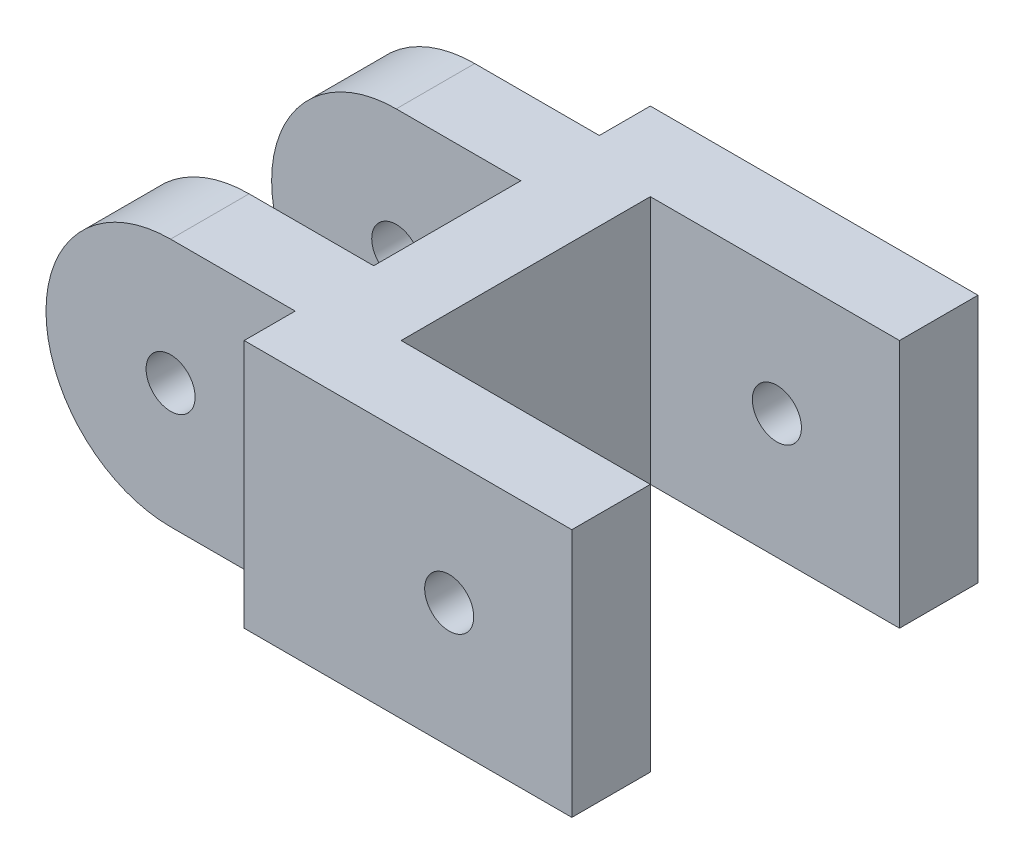
SolidWorks part; units mm, degrees
ref_plane "Front Plane" through (0, 0, 0) normal (0, 0, 1) x (1, 0, 0)
ref_plane "Top Plane" through (0, 0, 0) normal (0, 1, 0) x (1, 0, 0)
ref_plane "Right Plane" through (0, 0, 0) normal (1, 0, 0) x (0, 0, -1)
sketch "Sketch1" plane through (0, 0, 0) normal (0, 1, 0) x (1, 0, 0)
  line L0 (10.375, 15.95) -> (-15.025, 15.95)
  line L1 (-15.025, 15.95) -> (-15.025, -9.45)
  line L2 (-15.025, -9.45) -> (10.375, -9.45)
  line L3 (10.375, -9.45) -> (10.375, -17.45)
  line L4 (10.375, -17.45) -> (-23.025, -17.45)
  line L5 (-23.025, -17.45) -> (-23.025, -12.25)
  line L6 (-23.025, -12.25) -> (-48.425, -12.25)
  line L7 (-48.425, -12.25) -> (-48.425, -4.25)
  line L8 (-48.425, -4.25) -> (-23.025, -4.25)
  line L9 (-23.025, -4.25) -> (-23.025, 10.75)
  line L10 (-23.025, 10.75) -> (-48.425, 10.75)
  line L11 (-48.425, 10.75) -> (-48.425, 18.75)
  line L12 (-48.425, 18.75) -> (-23.025, 18.75)
  line L13 (-23.025, 18.75) -> (-23.025, 23.95)
  line L14 (-23.025, 23.95) -> (10.375, 23.95)
  line L15 (10.375, 23.95) -> (10.375, 15.95)
  dimension "D1" = 8
  dimension "D2" = 8
  dimension "D3" = 8
  dimension "D4" = 15
  dimension "D5" = 25.4
  dimension "D6" = 25.4
  dimension "D7" = 8
  dimension "D8" = 25.4
extrude "Boss-Extrude1" add sketch "Sketch1" along normal blind 25.4
fillet "Fillet1" radius 12.7 4 edges at (-48.425, 25.4, -14.75) (-48.425, 0, -14.75) (-48.425, 0, 8.25) (-48.425, 25.4, 8.25)
sketch "Sketch2" plane through (0, 0, 12.25) normal (0, 0, 1) x (1, 0, 0)
  circle A0 centre (-35.725, 12.7) radius 2.5
  dimension "D1" = 5
extrude "Cut-Extrude1" cut sketch "Sketch2" against normal up to surface (31 mm away) up to face at (-34.2371, 12.7, -18.75)
sketch "Sketch3" plane through (0, 0, 17.45) normal (0, 0, 1) x (1, 0, 0)
  line L0 (10.375, 25.4) -> (10.375, 0) construction
  circle A0 centre (-2.125, 12.7) radius 2.5
  dimension "D2" = 5
  dimension "D1" = 12.5
extrude "Cut-Extrude2" cut sketch "Sketch3" against normal up to surface (41.4 mm away) up to face at (-6.325, 12.7, -23.95)
